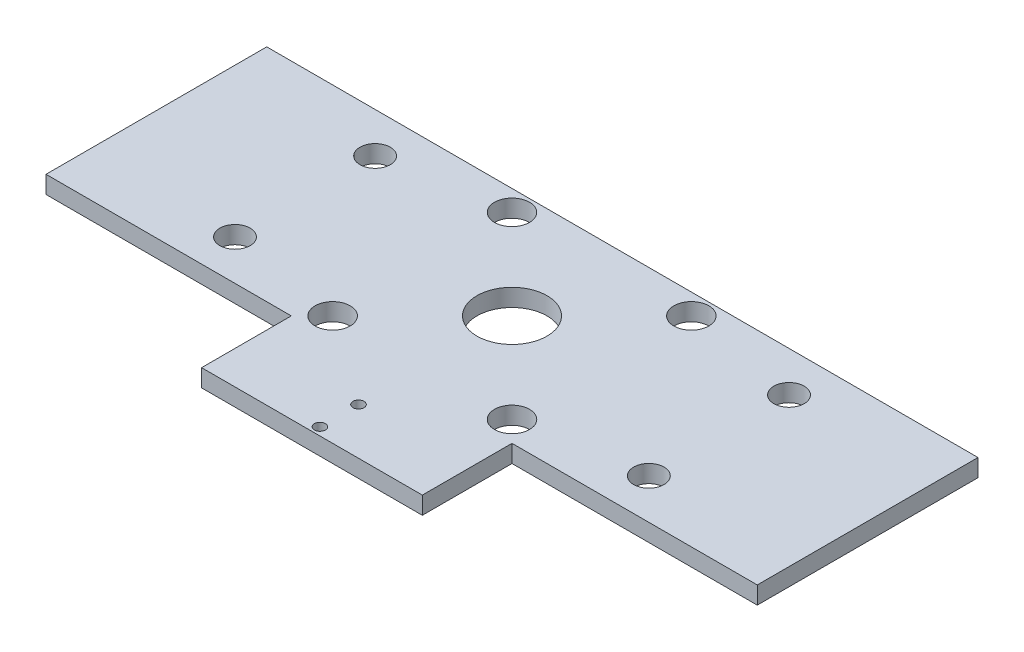
SolidWorks part; units mm, degrees
ref_plane "Front Plane" through (0, 0, 0) normal (0, 0, 1) x (1, 0, 0)
ref_plane "Top Plane" through (0, 0, 0) normal (0, 1, 0) x (1, 0, 0)
ref_plane "Right Plane" through (0, 0, 0) normal (1, 0, 0) x (0, 0, -1)
sketch "Sketch1" plane through (0, 0, 0) normal (0, 1, 0) x (1, 0, 0)
  line L0 (40, -40) -> (128.9, -40)
  line L1 (-128.9, 40) -> (128.9, 40)
  line L2 (-128.9, 40) -> (-128.9, -40)
  line L3 (-128.9, -40) -> (-40, -40)
  line L4 (128.9, 40) -> (128.9, -40)
  line L5 (-128.9, 40) -> (128.9, -40) construction
  line L6 (-128.9, -40) -> (128.9, 40) construction
  line L8 (-40, -40) -> (-40, -72.5)
  line L9 (-40, -72.5) -> (40, -72.5)
  line L10 (40, -40) -> (40, -72.5)
  point P0 (0, 0)
  point P10 (0, -72.5)
  dimension "D1" = 80
  dimension "D2" = 257.8
  dimension "D3" = 80
  dimension "D4" = 72.5
extrude "Boss-Extrude1" add sketch "Sketch1" along normal mid plane 6.35
hole_wizard "1 (1) Diameter Hole1" positions "Sketch3" profile "Sketch2" hole size "1" standard "ANSI Inch" end condition through all
sketch "Sketch3" plane through (0, 3.175, 0) normal (0, 1, 0) x (1, 0, 0)
  point P0 (0, 0)
sketch "Sketch2" plane through (0, 3.175, 0) normal (1, 0, 0) x (0, 0, 1)
  line L0 (0, 0) -> (0, 6.35)
  line L1 (0, 6.35) -> (12.7, 6.35)
  line L2 (12.7, 6.35) -> (12.7, 0)
  line L5 (12.7, 0) -> (0, 0)
  line L11 (0, -6.35) -> (0, 107.95) construction
  dimension "Thru Hole Dia." = 25.4
  dimension "Thru Hole Depth" = 6.35
hole_wizard "1/2 (0.5) Diameter Hole1" positions "Sketch5" profile "Sketch4" hole size "1/2" standard "ANSI Inch" end condition through all
sketch "Sketch5" plane through (0, 3.175, 0) normal (0, 1, 0) x (1, 0, 0)
  line L1 (-32.5, 32.5) -> (32.5, 32.5)
  line L2 (-32.5, 32.5) -> (-32.5, -32.5)
  line L3 (-32.5, -32.5) -> (32.5, -32.5)
  line L4 (32.5, 32.5) -> (32.5, -32.5)
  line L5 (-32.5, 32.5) -> (32.5, -32.5) construction
  line L6 (-32.5, -32.5) -> (32.5, 32.5) construction
  point P2 (32.5, -32.5)
  point P5 (-32.5, 32.5)
  point P6 (-32.5, -32.5)
  point P7 (32.5, 32.5)
  dimension "D1" = 65
sketch "Sketch4" plane through (32.5, 3.175, 32.5) normal (1, 0, 0) x (0, 0, 1)
  line L0 (0, 0) -> (0, 6.35)
  line L1 (0, 6.35) -> (6.35, 6.35)
  line L2 (6.35, 6.35) -> (6.35, 0)
  line L5 (6.35, 0) -> (0, 0)
  line L11 (0, -6.35) -> (0, 107.95) construction
  dimension "Thru Hole Dia." = 12.7
  dimension "Thru Hole Depth" = 6.35
hole_wizard "Ø4.0 (4) Diameter Hole1" positions "Sketch7" profile "Sketch6" hole size "Ø4.0" standard "ANSI Metric" end condition through all
sketch "Sketch7" plane through (0, 3.175, 0) normal (0, 1, 0) x (1, 0, 0)
  point P0 (0, -55.63)
  point P2 (0, -69.63)
  dimension "D1" = 55.63
  dimension "D2" = 14
sketch "Sketch6" plane through (0, 3.175, 55.63) normal (1, 0, 0) x (0, 0, 1)
  line L0 (0, 0) -> (0, 6.35)
  line L1 (0, 6.35) -> (2, 6.35)
  line L2 (2, 6.35) -> (2, 0)
  line L5 (2, 0) -> (0, 0)
  line L11 (0, -6.35) -> (0, 107.95) construction
  dimension "Thru Hole Dia." = 4
  dimension "Thru Hole Depth" = 6.35
hole_wizard "M10 Clearance Hole1" positions "Sketch9" profile "Sketch8" hole size "M10" standard "ANSI Metric" end condition through all
sketch "Sketch9" plane through (0, 3.175, 0) normal (0, 1, 0) x (1, 0, 0)
  line L1 (-75, 25.4) -> (75, 25.4)
  line L2 (-75, 25.4) -> (-75, -25.4)
  line L3 (-75, -25.4) -> (75, -25.4)
  line L4 (75, 25.4) -> (75, -25.4)
  line L5 (-75, 25.4) -> (75, -25.4) construction
  line L6 (-75, -25.4) -> (75, 25.4) construction
  point P2 (75, -25.4)
  point P5 (-75, 25.4)
  point P6 (-75, -25.4)
  point P7 (75, 25.4)
  dimension "D1" = 50.8
  dimension "D2" = 150
sketch "Sketch8" plane through (75, 3.175, 25.4) normal (1, 0, 0) x (0, 0, 1)
  line L0 (0, 0) -> (0, 6.35)
  line L1 (0, 6.35) -> (5.5, 6.35)
  line L2 (5.5, 6.35) -> (5.5, 0)
  line L5 (5.5, 0) -> (0, 0)
  line L11 (0, -6.35) -> (0, 107.95) construction
  dimension "Thru Hole Dia." = 11
  dimension "Thru Hole Depth" = 6.35
